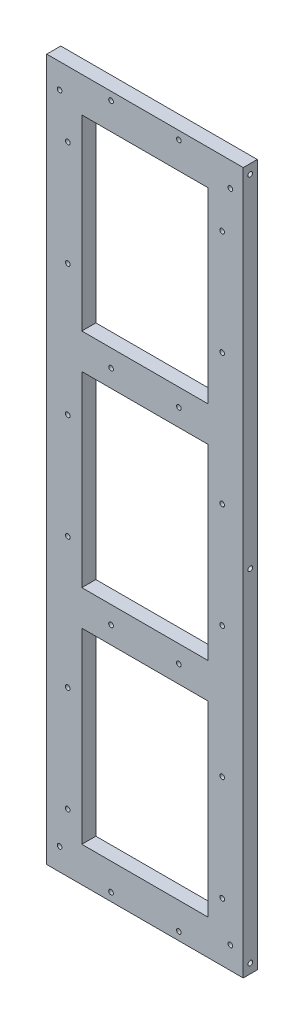
SolidWorks part; units mm, degrees
material "Alumina"
ref_plane "Front Plane" through (0, 0, 0) normal (0, 0, 1) x (1, 0, 0)
ref_plane "Top Plane" through (0, 0, 0) normal (0, 1, 0) x (1, 0, 0)
ref_plane "Right Plane" through (0, 0, 0) normal (1, 0, 0) x (0, 0, -1)
sketch "Sketch1" plane through (0, 0, 0) normal (0, 0, 1) x (1, 0, 0)
  line L0 (27, 135) -> (27, 55)
  line L9 (-42, -150) -> (42, -150)
  line L10 (-42, -150) -> (-42, 150)
  line L11 (-42, 150) -> (42, 150)
  line L12 (42, -150) -> (42, 150)
  line L13 (0, 0) -> (0, 40) construction
  line L15 (-27, -135) -> (27, -135)
  line L16 (-27, -135) -> (-27, -55)
  line L17 (-27, 135) -> (27, 135)
  line L21 (-27, 55) -> (27, 55)
  line L23 (-27, 40) -> (27, 40)
  line L25 (-27, -40) -> (27, -40)
  line L27 (-27, -55) -> (27, -55)
  line L33 (27, 40) -> (27, -40)
  line L34 (-27, 55) -> (-27, 135)
  line L35 (-27, -40) -> (-27, 40)
  line L36 (27, -55) -> (27, -135)
  dimension "D1" = 84
  dimension "D2" = 300
  dimension "D3" = 54
  dimension "D4" = 270
  dimension "D5" = 15
  dimension "D6" = 80
  dimension "D7" = 15
  dimension "D8" = 80
  dimension "D9" = 15
  dimension "D10" = 15
  dimension "D11" = 80
  dimension "D12" = 40
  dimension "D13" = 15
extrude "Boss-Extrude1" add sketch "Sketch1" along normal blind 6
sketch "Sketch2" plane through (42, 0, 0) normal (1, 0, 0) x (0, 0, -1)
  line L0 (-6, 150) -> (0, 150) construction
  line L1 (-6, -150) -> (-6, 150) construction
  line L3 (-3, 146) -> (-3, 0) construction
  circle A0 centre (-3, 146) radius 1
  circle A4 centre (-3, 0) radius 1
  circle A5 centre (-3, -146) radius 1
  circle A6 centre (-3, -292) radius 1
  dimension "D1" = 4
  dimension "D3" = 2
  dimension "D4" = 3
  dimension "D2" = 4
  dimension "D5" = 146
extrude "Cut-Extrude1" cut sketch "Sketch2" against normal blind 10
mirror "Mirror1" about plane through (0, 0, 0) normal (1, 0, 0) of "Cut-Extrude1"
sketch "Sketch4" plane through (0, 0, 6) normal (0, 0, 1) x (1, 0, 0)
  line L0 (-42, -150) -> (-42, 150) construction
  line L2 (-42, 150) -> (42, 150) construction
  line L3 (42, 150) -> (-42, 150) construction
  line L4 (-42, -150) -> (42, -150) construction
  line L5 (-42, 150) -> (-42, -150) construction
  line L6 (27, -55) -> (-27, -55) construction
  line L7 (27, 40) -> (-27, 40) construction
  line L8 (-33, 122) -> (-33, -125) construction
  line L9 (0, -3.3) -> (0, 3.3) construction
  line L10 (33, 122) -> (33, -125) construction
  circle A0 centre (-14.5, 146.5) radius 1
  circle A8 centre (-33, 122) radius 1
  circle A20 centre (-14.5, 47.5) radius 1
  circle A22 centre (-14.5, -47.5) radius 1
  circle A24 centre (-14.5, -146.5) radius 1
  circle A40 centre (-33, -125) radius 1
  circle A41 centre (-33, 77) radius 1
  circle A42 centre (-33, -80) radius 1
  circle A43 centre (-33, 21) radius 1
  circle A44 centre (-33, -24) radius 1
  circle A45 centre (33, -24) radius 1
  circle A46 centre (33, 21) radius 1
  circle A47 centre (33, -80) radius 1
  circle A48 centre (33, 77) radius 1
  circle A49 centre (33, -125) radius 1
  circle A50 centre (14.5, -146.5) radius 1
  circle A51 centre (14.5, -47.5) radius 1
  circle A52 centre (14.5, 47.5) radius 1
  circle A53 centre (33, 122) radius 1
  circle A54 centre (14.5, 146.5) radius 1
  dimension "D1" = 27.5
  dimension "D4" = 27.5
  dimension "D7" = 2
  dimension "D10" = 2
  dimension "D11" = 7.5
  dimension "D3" = 3.5
  dimension "D6" = 25
  dimension "D14" = 2
  dimension "D15" = 27.5
  dimension "D16" = 2
  dimension "D17" = 2
  dimension "D12" = 2
  dimension "D2" = 3.5
  dimension "D8" = 7.5
  dimension "D18" = 2
  dimension "D19" = 45
  dimension "D20" = 2
  dimension "D22" = 2
  dimension "D23" = 2
  dimension "D24" = 45
  dimension "D25" = 56
  dimension "D21" = 56
  dimension "D5" = 28
  dimension "D9" = 9
  dimension "D13" = 27.5
extrude "Cut-Extrude3" cut sketch "Sketch4" against normal blind 10
sketch "Sketch5" plane through (0, 0, 6) normal (0, 0, 1) x (1, 0, 0)
  line L0 (-36.5, 139.5) -> (36.5, 139.5) construction
  line L1 (36.5, 139.5) -> (36.5, -140.5) construction
  line L2 (36.5, -140.5) -> (-36.5, -140.5) construction
  line L3 (-36.5, -140.5) -> (-36.5, 139.5) construction
  line L4 (-42, 150) -> (-42, -150) construction
  line L5 (42, 150) -> (-42, 150) construction
  line L6 (42, -150) -> (42, 150) construction
  line L7 (-42, -150) -> (42, -150) construction
  circle A0 centre (-36.5, -140.5) radius 1
  circle A1 centre (36.5, -140.5) radius 1
  circle A2 centre (-36.5, 139.5) radius 1
  circle A3 centre (36.5, 139.5) radius 1
  dimension "D5" = 2
  dimension "D6" = 2
  dimension "D7" = 2
  dimension "D8" = 2
  dimension "D1" = 5.5
  dimension "D2" = 10.5
  dimension "D3" = 5.5
  dimension "D4" = 9.5
extrude "Cut-Extrude4" cut sketch "Sketch5" against normal blind 10
